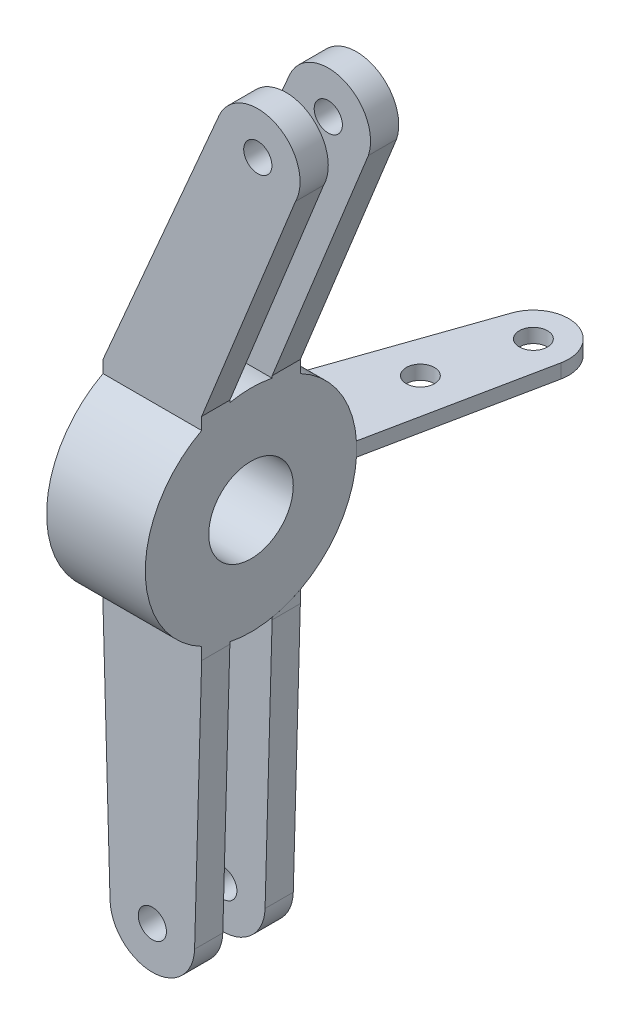
SolidWorks part; units mm, degrees
material "201.0-T6 Insulated Mold Casting (SS)"
ref_plane "Front Plane" through (0, 0, 0) normal (0, 0, 1) x (1, 0, 0)
ref_plane "Top Plane" through (0, 0, 0) normal (0, 1, 0) x (1, 0, 0)
ref_plane "Right Plane" through (0, 0, 0) normal (1, 0, 0) x (0, 0, -1)
sketch "Sketch1" plane through (0, 0, 0) normal (1, 0, 0) x (0, 0, -1)
  circle A0 centre (0, 0) radius 15
  circle A1 centre (0, 0) radius 37.5
  dimension "D1" = 30
  dimension "D2" = 75
extrude "Boss-Extrude1" add sketch "Sketch1" along normal mid plane 35
sketch "Sketch2" plane through (0, 0, 0) normal (0, 0, 1) x (1, 0, 0)
  line L0 (0, 37.5) -> (37.4154, 127) construction
  line L2 (0, -37.5) -> (0, -127) construction
  line L4 (0, -127) -> (37.4154, 127) construction
  line L6 (-17.5, 37.5) -> (23.8168, 133.3306)
  line L7 (17.5, 37.5) -> (-17.5, 37.5) construction
  line L8 (-17.5, 37.5) -> (17.5, 37.5)
  line L10 (-17.5, 37.5) -> (-17.5, -37.5) construction
  line L11 (17.5, -37.5) -> (14.9942, -127.4179)
  line L12 (-17.5, -37.5) -> (-14.9942, -127.4179)
  line L13 (-17.5, -37.5) -> (17.5, -37.5) construction
  line L14 (-17.5, -37.5) -> (17.5, -37.5)
  line L15 (51.63, 122.2096) -> (17.5, 37.5)
  circle A0 centre (37.4154, 127) radius 5
  arc A2 (51.63, 122.2096) -> (23.8168, 133.3306) centre (37.4154, 127) ccw
  circle A3 centre (0, -127) radius 5
  arc A4 (-14.9942, -127.4179) -> (14.9942, -127.4179) centre (0, -127) ccw
  dimension "D4" = 10
  dimension "D5" = 203.323
  dimension "D6" = 15
  dimension "D8" = 30
  dimension "D9" = 10
  dimension "D2" = 127
  dimension "D3" = 127
  dimension "D7" = 84.7096
ref_plane "Plane1" through (0, 0, 7.5) normal (0, 0, 1) x (1, 0, 0)
sketch "Sketch4" plane through (0, 0, 7.5) normal (0, 0, 1) x (1, 0, 0)
  line L0 (-17.5, -37.5) -> (-14.9942, -127.4179) construction
  line L1 (17.5, -37.5) -> (14.9942, -127.4179) construction
  line L2 (-17.5, -37.5) -> (17.5, -37.5) construction
  line L5 (-17.5, 37.5) -> (23.8168, 133.3306) construction
  line L6 (-17.5, -37.5) -> (-14.9942, -127.4179)
  line L7 (17.5, -37.5) -> (14.9942, -127.4179)
  line L8 (-17.5, -37.5) -> (17.5, -37.5)
  line L11 (-17.5, 37.5) -> (23.8168, 133.3306)
  line L12 (-17.5, 37.5) -> (17.5, 37.5)
  line L14 (17.5, 37.5) -> (50.7583, 120.1467)
  circle A0 centre (0, -127) radius 5 construction
  arc A1 (-14.9942, -127.4179) -> (14.9942, -127.4179) centre (0, -127) ccw construction
  circle A2 centre (37.4154, 127) radius 5 construction
  circle A4 centre (0, -127) radius 5
  arc A5 (-14.9942, -127.4179) -> (14.9942, -127.4179) centre (0, -127) ccw
  circle A6 centre (37.4154, 127) radius 5
  arc A8 (50.7583, 120.1467) -> (23.8168, 133.3306) centre (37.4154, 127) ccw
ref_plane "Plane2" through (0, 0, -7.5) normal (0, 0, 1) x (1, 0, 0)
sketch "Sketch5" plane through (0, 0, -7.5) normal (0, 0, 1) x (1, 0, 0)
  line L0 (-17.5, -37.5) -> (-14.9942, -127.4179) construction
  line L1 (17.5, -37.5) -> (14.9942, -127.4179) construction
  line L2 (-17.5, -37.5) -> (17.5, -37.5) construction
  line L3 (-17.5, 37.5) -> (17.5, 37.5) construction
  line L5 (-17.5, 37.5) -> (23.8168, 133.3306) construction
  line L6 (-17.5, -37.5) -> (-14.9942, -127.4179)
  line L7 (17.5, -37.5) -> (14.9942, -127.4179)
  line L8 (-17.5, -37.5) -> (17.5, -37.5)
  line L9 (-17.5, 37.5) -> (17.5, 37.5)
  line L11 (-17.5, 37.5) -> (23.8168, 133.3306)
  line L12 (17.5, 37.5) -> (51.63, 122.2096)
  circle A0 centre (0, -127) radius 5 construction
  arc A1 (-14.9942, -127.4179) -> (14.9942, -127.4179) centre (0, -127) ccw construction
  circle A2 centre (37.4154, 127) radius 5 construction
  arc A3 (51.63, 122.2096) -> (23.8168, 133.3306) centre (37.4154, 127) ccw construction
  circle A4 centre (0, -127) radius 5
  arc A5 (-14.9942, -127.4179) -> (14.9942, -127.4179) centre (0, -127) ccw
  circle A6 centre (37.4154, 127) radius 5
  arc A7 (51.63, 122.2096) -> (23.8168, 133.3306) centre (37.4154, 127) ccw
extrude "Boss-Extrude3" add sketch "Sketch5" against normal blind 10 separate body
extrude "Boss-Extrude5" add sketch "Sketch4" along normal blind 10 separate body
sketch "Sketch7" plane through (17.5, 0, 0) normal (1, 0, 0) x (0, 0, -1)
  line L0 (-17.5, 37.5) -> (-17.5, 33.1662)
  line L1 (-7.5, 37.5) -> (-7.5, 36.7423)
  line L2 (-17.5, 37.5) -> (-7.5, 37.5)
  line L3 (7.5, 37.5) -> (7.5, 36.3048)
  line L7 (7.5, -37.5) -> (7.5, -36.7423)
  line L8 (7.5, -37.5) -> (17.5, -37.5)
  line L9 (17.5, -37.5) -> (17.5, -33.1662)
  line L10 (-7.5, -37.5) -> (-7.5, -36.7423)
  line L11 (-7.5, -37.5) -> (-17.5, -37.5)
  line L14 (7.5, 37.5) -> (17.5, 37.5)
  line L15 (17.5, 37.5) -> (17.5, 33.1662)
  line L16 (-17.5, -37.5) -> (-17.5, -33.1662)
  arc A2 (-7.5, 36.7423) -> (-17.5, 33.1662) centre (0.851, -2.3797) ccw
  arc A3 (17.5, 33.1662) -> (7.5, 36.3048) centre (0.851, -2.3797) ccw
  arc A4 (7.5, -36.7423) -> (17.5, -33.1662) centre (0.851, -2.3797) ccw
  circle A5 centre (0, 0) radius 37.5 construction
  arc A6 (-17.5, -33.1662) -> (-7.5, -36.7423) centre (0, 0) ccw
  arc A7 (7.5, -36.7423) -> (17.5, -33.1662) centre (0, 0) ccw
  arc A8 (17.5, 33.1662) -> (-17.5, 33.1662) centre (0, 0) ccw
  circle M2 centre (0, 0) radius 37.5
sketch "Sketch10" plane through (0, 0, 0) normal (0, 1, 0) x (1, 0, 0)
  line L0 (17.5085, 100.1663) -> (0, 37.5) construction
  line L2 (-17.5, 37.5) -> (17.5, 37.5)
  line L3 (17.5, 37.5) -> (29.757, 97.6713)
  line L4 (5.7011, 104.2692) -> (-17.5, 37.5)
  line L5 (17.5, -37.5) -> (17.5, 37.5) construction
  circle A0 centre (17.5085, 100.1663) radius 5
  arc A1 (29.757, 97.6713) -> (5.7011, 104.2692) centre (17.5085, 100.1663) ccw
  circle A2 centre (8.7543, 68.8331) radius 5
  dimension "D2" = 10
  dimension "D3" = 25
  dimension "D6" = 10
  dimension "D1" = 70.839
  dimension "D4" = 168.486
  dimension "D5" = 74.39
  dimension "D7" = 32.5331
extrude "Boss-Extrude8" add sketch "Sketch10" along normal mid plane 5 separate body
sketch "Sketch11" plane through (17.5, 0, 0) normal (1, 0, 0) x (0, 0, -1)
  line L0 (37.5, -2.5) -> (34.4498, -2.5)
  line L1 (34.4498, -2.5) -> (37.479, -1.254)
  line L2 (37.5, 2.5) -> (34.5567, 2.5)
  line L3 (34.5567, 2.5) -> (37.479, -1.254)
  line L4 (37.5, 2.5) -> (37.5, -2.5)
  circle A0 centre (0, 0) radius 37.5 construction
  arc A1 (37.5, 0) -> (37.4166, 2.5) centre (0, 0) ccw
  circle M10 centre (0, 0) radius 37.5
extrude "Boss-Extrude9" add sketch "Sketch11" against normal up to surface (35 mm away) contours L4 L0 M10 | L1 L0 M10 | L4 L2 M10 | L2 L3 M10 region at (17.5, -1.8751, -37.475) region at (17.5, -2.0842, -36.4508) region at (17.5, 1.8751, -37.475) region at (17.5, 1.2353, -36.5052) up to face at (-17.5, 0, -37.5)
extrude "Boss-Extrude10" add sketch "Sketch7" against normal up to surface (35 mm away) contours L15 L14 L3 M2 | L16 L11 L10 M2 | L8 L9 L7 M2 | L0 L2 L1 A2 region at (17.5, -36.1261, 13.8023) region at (17.5, 36.1261, -13.8023) region at (17.5, -36.1337, -13.8125) up to face at (-17.5, 0, -37.5)
